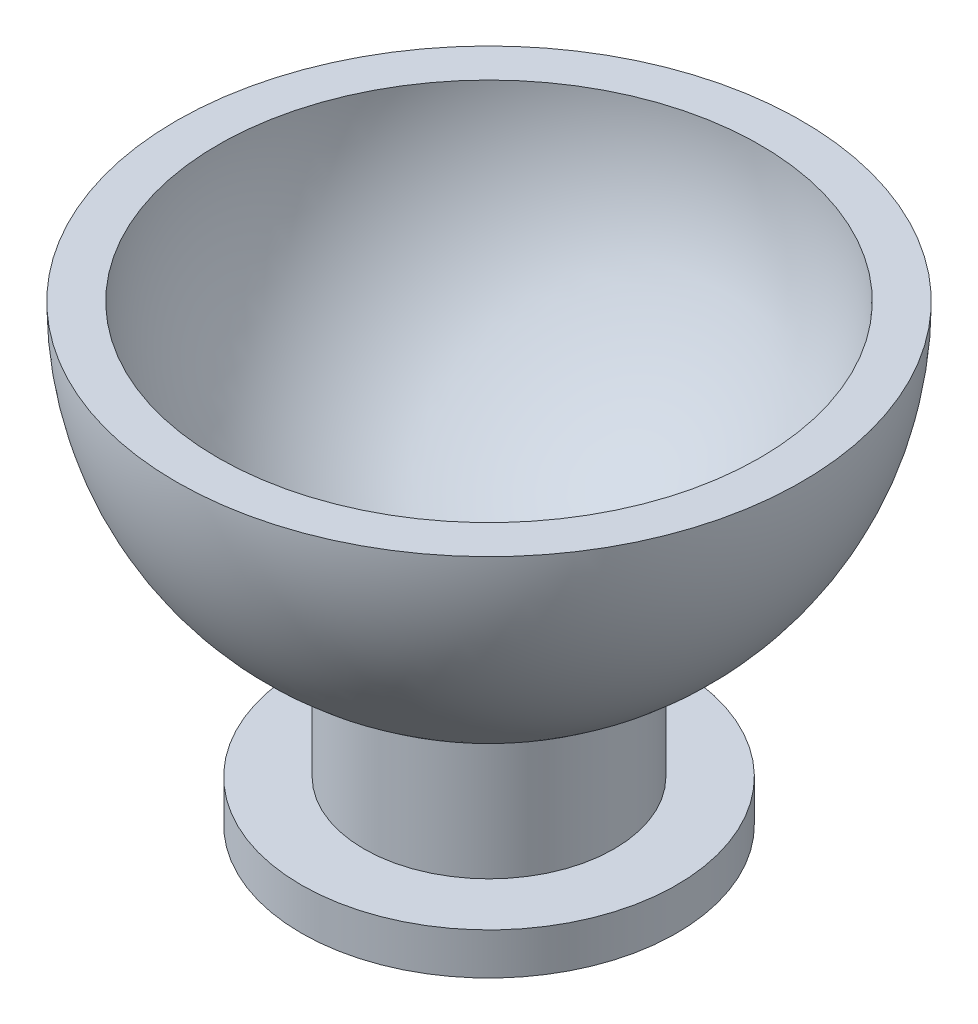
SolidWorks part; units mm, degrees
ref_plane "Front Plane" through (0, 0, 0) normal (0, 0, 1) x (1, 0, 0)
ref_plane "Top Plane" through (0, 0, 0) normal (0, 1, 0) x (1, 0, 0)
ref_plane "Right Plane" through (0, 0, 0) normal (1, 0, 0) x (0, 0, -1)
sketch "Sketch2" plane through (0, 0, 0) normal (0, 1, 0) x (1, 0, 0)
  circle A0 centre (0, 0) radius 11.43
  dimension "D1" = 22.86
extrude "Boss-Extrude1" add sketch "Sketch2" along normal blind 2.54
sketch "Sketch3" plane through (0, 2.54, 0) normal (0, 1, 0) x (1, 0, 0)
  circle A0 centre (0, 0) radius 7.62
  dimension "D1" = 15.24
extrude "Boss-Extrude2" add sketch "Sketch3" along normal blind 7.62
sketch "Sketch5" plane through (0, 0, 0) normal (0, 0, 1) x (1, 0, 0)
  line L1 (0, 47.8751) -> (0, 7.0617) construction
  line L4 (16.51, 27.6196) -> (19.05, 27.6196)
  line L5 (0, 8.5696) -> (0, 11.1096)
  arc A2 (0, 8.5696) -> (19.05, 27.6196) centre (0, 27.6196) ccw
  arc A3 (0, 11.1096) -> (16.51, 27.6196) centre (0, 27.6196) ccw
  dimension "D2" = 2.54
  dimension "D1" = 38.1
revolve "Revolve1" add sketch "Sketch5" angle 360 about L1
